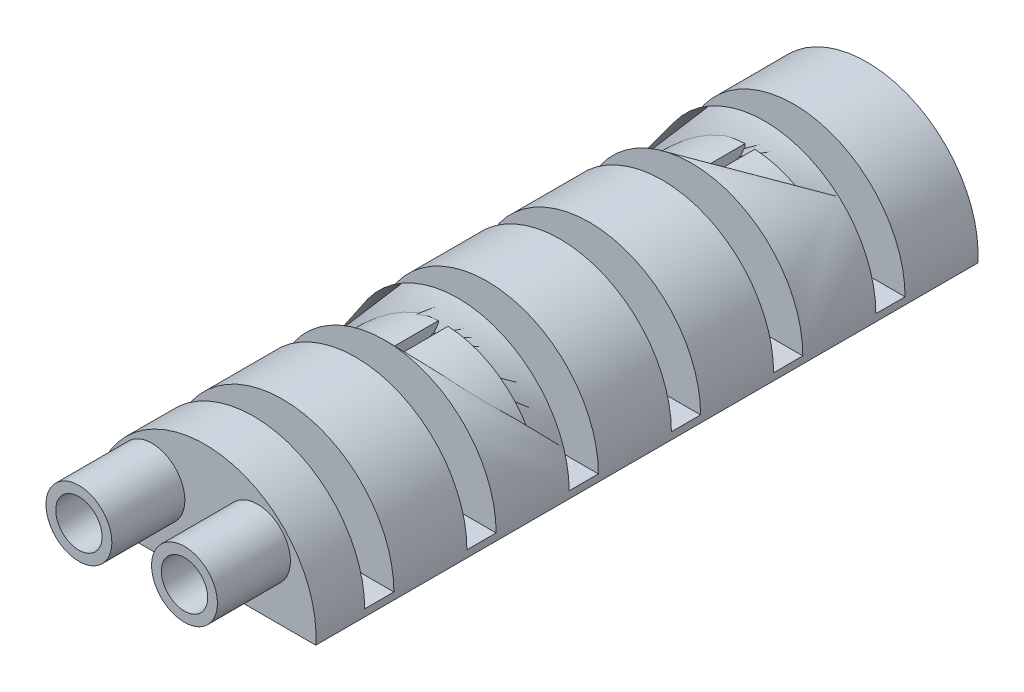
SolidWorks part; units mm, degrees
material "RUBBER 65A"
ref_plane "Front Plane" through (0, 0, 0) normal (0, 0, 1) x (1, 0, 0)
ref_plane "Top Plane" through (0, 0, 0) normal (0, 1, 0) x (1, 0, 0)
ref_plane "Right Plane" through (0, 0, 0) normal (1, 0, 0) x (0, 0, -1)
sketch "Sketch3" plane through (0, 0, 0) normal (0, 0, 1) x (1, 0, 0)
  circle A0 centre (0, 0) radius 22.86
  dimension "D1" = 45.72
extrude "Boss-Extrude2" add sketch "Sketch3" along normal blind 175
ref_axis "Axis2" through (0, 0, 174.1287) along (0, 0, -1)
sketch "Sketch5" plane through (0, 0, 175) normal (0, 0, 1) x (1, 0, 0)
  circle A0 centre (0, 0) radius 3.175
  dimension "D1" = 6.35
extrude "Cut-Extrude1" cut sketch "Sketch5" against normal through all contours A0
sketch "Sketch4" plane through (0, 0, 0) normal (0, 1, 0) x (1, 0, 0)
  line L0 (0, -175) -> (0, 0) construction
  line L1 (-22.86, -175) -> (22.86, -175) construction
  line L3 (-27.5, -165) -> (-11.5, -165)
  line L4 (-27.5, -165) -> (-27.5, -159)
  line L5 (-27.5, -159) -> (-11.5, -159)
  line L6 (-11.5, -165) -> (-11.5, -159)
  line L63 (-27.5, -144) -> (-27.5, -138)
  line L64 (-27.5, -144) -> (-11.5, -144)
  line L65 (-11.5, -144) -> (-11.5, -138)
  line L66 (-27.5, -138) -> (-11.5, -138)
  line L67 (-27.5, -123) -> (-27.5, -117)
  line L68 (-27.5, -123) -> (-11.5, -123)
  line L69 (-11.5, -123) -> (-11.5, -117)
  line L70 (-27.5, -117) -> (-11.5, -117)
  line L71 (-27.5, -102) -> (-27.5, -96)
  line L72 (-27.5, -102) -> (-11.5, -102)
  line L73 (-11.5, -102) -> (-11.5, -96)
  line L74 (-27.5, -96) -> (-11.5, -96)
  line L75 (-27.5, -81) -> (-27.5, -75)
  line L76 (-27.5, -81) -> (-11.5, -81)
  line L77 (-11.5, -81) -> (-11.5, -75)
  line L78 (-27.5, -75) -> (-11.5, -75)
  line L79 (-27.5, -60) -> (-27.5, -54)
  line L80 (-27.5, -60) -> (-11.5, -60)
  line L81 (-11.5, -60) -> (-11.5, -54)
  line L82 (-27.5, -54) -> (-11.5, -54)
  line L83 (-27.5, -39) -> (-27.5, -33)
  line L84 (-27.5, -39) -> (-11.5, -39)
  line L85 (-11.5, -39) -> (-11.5, -33)
  line L86 (-27.5, -33) -> (-11.5, -33)
  line L87 (-27.5, -18) -> (-27.5, -12)
  line L88 (-27.5, -18) -> (-11.5, -18)
  line L89 (-11.5, -18) -> (-11.5, -12)
  line L90 (-27.5, -12) -> (-11.5, -12)
  line L91 (-27.5, -165) -> (-27.5, -144) construction
  dimension "D1" = 10
  dimension "D2" = 6
  dimension "D3" = 27.5
  dimension "D4" = 16
  dimension "D6" = 21
  dimension "D5" = 8
revolve "Cut-Revolve1" cut sketch "Sketch4" angle 360 about L0
shell "Shell1" thickness 3
sketch "Sketch10" plane through (0, 0, 0) normal (0, 0, -1) x (-1, 0, 0)
  line L0 (0, 22.86) -> (0, -22.86) construction
  line L1 (-22.86, 0) -> (22.86, 0) construction
  line L2 (-1, 22.8381) -> (-1, 3.0134)
  line L3 (1, 3.0134) -> (1, 22.8381)
  line L4 (3.0134, 1) -> (22.8381, 1)
  line L5 (3.0134, -1) -> (22.8381, -1)
  line L6 (-1, -3.0134) -> (-1, -22.8381)
  line L7 (1, -3.0134) -> (1, -22.8381)
  line L8 (-22.8381, -1) -> (-3.0134, -1)
  line L9 (-22.8381, 1) -> (-3.0134, 1)
  circle A0 centre (0, 0) radius 22.86 construction
  circle A1 centre (0, 0) radius 3.175 construction
  arc A2 (-1, -22.8381) -> (1, -22.8381) centre (0, 0) ccw
  arc A3 (22.8381, -1) -> (22.8381, 1) centre (0, 0) ccw
  arc A4 (1, 22.8381) -> (-1, 22.8381) centre (0, 0) ccw
  arc A5 (-22.8381, 1) -> (-22.8381, -1) centre (0, 0) ccw
  arc A6 (-1, -3.0134) -> (1, -3.0134) centre (0, 0) ccw
  arc A7 (-3.0134, 1) -> (-3.0134, -1) centre (0, 0) ccw
  arc A8 (1, 3.0134) -> (-1, 3.0134) centre (0, 0) ccw
  arc A9 (3.0134, -1) -> (3.0134, 1) centre (0, 0) ccw
  dimension "D1" = 1
  dimension "D2" = 1
  dimension "D3" = 1
  dimension "D4" = 1
  dimension "D5" = 1
extrude "Boss-Extrude3" add sketch "Sketch10" against normal up to surface (175 mm away) up to face at (3.175, 0, 175)
sketch "Sketch11" plane through (0, 0, 0) normal (1, 0, 0) x (0, 0, -1)
  line L0 (-117, 22.8381) -> (-117, 1) construction
  line L1 (-165, 30.0791) -> (-159, 30.0791)
  line L2 (-165, 30.0791) -> (-165, 11.4564)
  line L3 (-165, 11.4564) -> (-159, 11.4564)
  line L4 (-159, 30.0791) -> (-159, 11.4564)
  line L5 (-144, 30.0191) -> (-138, 30.0191)
  line L6 (-144, 30.0191) -> (-144, 11.4564)
  line L7 (-144, 11.4564) -> (-138, 11.4564)
  line L8 (-138, 30.0191) -> (-138, 11.4564)
  line L9 (-123, 30.1992) -> (-117, 30.1992)
  line L10 (-123, 30.1992) -> (-123, 11.4755)
  line L11 (-123, 11.4755) -> (-117, 11.4755)
  line L12 (-117, 30.1992) -> (-117, 11.4755)
  line L13 (-117, 11.4564) -> (-117, 1) construction
  line L14 (-75, 11.4564) -> (-75, 1) construction
  line L15 (-102, 30.5593) -> (-96, 30.5593)
  line L16 (-102, 30.5593) -> (-102, 11.4564)
  line L17 (-102, 11.4564) -> (-96, 11.4564)
  line L18 (-96, 30.5593) -> (-96, 11.4564)
  line L19 (-81, 30.9195) -> (-75, 30.9195)
  line L20 (-81, 30.9195) -> (-81, 11.4755)
  line L21 (-81, 11.4755) -> (-75, 11.4755)
  line L22 (-75, 30.9195) -> (-75, 11.4755)
  line L23 (-75, 22.8381) -> (-75, 1) construction
  line L25 (-60, 31.9241) -> (-54, 31.9241)
  line L26 (-60, 31.9241) -> (-60, 11.4564)
  line L27 (-60, 11.4564) -> (-54, 11.4564)
  line L28 (-54, 31.9241) -> (-54, 11.4564)
  line L29 (-39, 30.6232) -> (-33, 30.6232)
  line L30 (-39, 30.6232) -> (-39, 11.4564)
  line L31 (-39, 11.4564) -> (-33, 11.4564)
  line L32 (-33, 30.6232) -> (-33, 11.4564)
  line L33 (-18, 31.5847) -> (-12, 31.5847)
  line L34 (-18, 31.5847) -> (-18, 11.4564)
  line L35 (-18, 11.4564) -> (-12, 11.4564)
  line L36 (-12, 31.5847) -> (-12, 11.4564)
revolve "Cut-Revolve2" cut sketch "Sketch11" angle 360 about axis through (0, 0, 174.1287) along (0, 0, -1)
sketch "Sketch12" plane through (0, 0, 0) normal (0, 1, 0) x (1, 0, 0)
  line L0 (19.8348, -172) -> (6.0935, -172) construction
  line L1 (24.7296, -168) -> (23.4796, -168)
  line L2 (24.7296, -168) -> (24.7296, -172)
  line L3 (24.7296, -172) -> (23.4796, -172)
  line L4 (23.4796, -168) -> (23.4796, -172)
  line L5 (0, 0) -> (0, -175) construction
  line L6 (-3.175, -175) -> (3.175, -175) construction
  line L7 (19.8348, -156) -> (8.441, -156) construction
  line L8 (19.8348, -9) -> (8.441, -9) construction
  line L9 (24.7296, -3) -> (23.4796, -3)
  line L10 (24.7296, -3) -> (24.7296, -9)
  line L11 (24.7296, -9) -> (23.4796, -9)
  line L12 (23.4796, -3) -> (23.4796, -9)
  line L13 (24.7296, -147) -> (23.4796, -147)
  line L14 (24.7296, -147) -> (24.7296, -156)
  line L15 (24.7296, -156) -> (23.4796, -156)
  line L16 (23.4796, -147) -> (23.4796, -156)
  line L17 (19.8348, -135) -> (8.441, -135) construction
  line L18 (24.7296, -126) -> (23.4796, -126)
  line L19 (24.7296, -126) -> (24.7296, -135)
  line L20 (24.7296, -135) -> (23.4796, -135)
  line L21 (23.4796, -126) -> (23.4796, -135)
  line L22 (19.8348, -114) -> (8.441, -114) construction
  line L23 (24.7296, -105) -> (23.4796, -105)
  line L24 (24.7296, -105) -> (24.7296, -114)
  line L25 (24.7296, -114) -> (23.4796, -114)
  line L26 (23.4796, -105) -> (23.4796, -114)
  line L27 (19.8348, -93) -> (8.441, -93) construction
  line L28 (24.7296, -84) -> (23.4796, -84)
  line L29 (24.7296, -84) -> (24.7296, -93)
  line L30 (24.7296, -93) -> (23.4796, -93)
  line L31 (23.4796, -84) -> (23.4796, -93)
  line L32 (19.8348, -72) -> (8.441, -72) construction
  line L33 (24.7296, -63) -> (23.4796, -63)
  line L34 (24.7296, -63) -> (24.7296, -72)
  line L35 (24.7296, -72) -> (23.4796, -72)
  line L36 (23.4796, -63) -> (23.4796, -72)
  line L37 (19.8348, -51) -> (8.441, -51) construction
  line L38 (24.7296, -42) -> (23.4796, -42)
  line L39 (24.7296, -42) -> (24.7296, -51)
  line L40 (24.7296, -51) -> (23.4796, -51)
  line L41 (23.4796, -42) -> (23.4796, -51)
  line L42 (19.8348, -30) -> (8.441, -30) construction
  line L43 (24.7296, -21) -> (23.4796, -21)
  line L44 (24.7296, -21) -> (24.7296, -30)
  line L45 (24.7296, -30) -> (23.4796, -30)
  line L46 (23.4796, -21) -> (23.4796, -30)
  dimension "D1" = 1.25
  dimension "D2" = 1.25
  dimension "D3" = 1.25
  dimension "D4" = 1.25
  dimension "D5" = 1.25
  dimension "D6" = 1.25
  dimension "D7" = 1.25
  dimension "D8" = 1.25
  dimension "D9" = 1.25
ref_plane "Plane1" through (0, 0, 0) normal (-0.7071, -0.7071, 0) x (0, 0, -1)
ref_plane "Plane2" through (0, 0, 0) normal (-0.7071, 0.7071, 0) x (0, 0, -1)
sketch "Sketch13" plane through (0, 0, 175) normal (0, 0, 1) x (1, 0, 0)
  line L0 (0, 22.86) -> (0, -22.86) construction
  line L1 (22.86, 0) -> (-22.86, 0) construction
  line L2 (0, 0) -> (16.1645, 16.1645) construction
  line L3 (22.3322, 22.3322) -> (-22.3322, -22.3322) construction
  circle A0 centre (10.8453, 10.8453) radius 6.7625
  circle A1 centre (10.8453, 10.8453) radius 4.7625
  circle A2 centre (0, 0) radius 15.3375 construction
  circle A3 centre (0, 0) radius 22.86 construction
  dimension "D1" = 2
  dimension "D2" = 9.525
  dimension "D3" = 30.675
extrude "Boss-Extrude4" add sketch "Sketch13" along normal blind 15
sketch "Sketch14" plane through (0, 0, 190) normal (0, 0, 1) x (1, 0, 0)
  circle A0 centre (10.8453, 10.8453) radius 4.7625
  dimension "D1" = 9.525
extrude "Cut-Extrude2" cut sketch "Sketch14" against normal blind 18
pattern_circular "CirPattern1" count 2 over 90 about axis through (0, 0, 174.1287) along (0, 0, -1) of "Boss-Extrude4", "Cut-Extrude2"
sketch "Sketch15" plane through (0, 0, 0) normal (0, 0, -1) x (-1, 0, 0)
  circle A0 centre (0, 0) radius 26.7427
extrude "Cut-Extrude3" cut sketch "Sketch15" against normal up to surface (39 mm away)
sketch "Sketch16" plane through (0, 0, 39) normal (0, 0, -1) x (-1, 0, 0)
  circle A0 centre (0, 0) radius 8.5
  circle A1 centre (0, 0) radius 3.175
extrude "Boss-Extrude6" add sketch "Sketch16" against normal up to surface (3 mm away) up to face at (-8.7979, 8.7979, 42)
sketch "Sketch17" plane through (0, 0, 175) normal (0, 0, 1) x (1, 0, 0)
  line L0 (-3.1748, 0) -> (-22.86, 0)
  line L1 (3.1748, 0) -> (22.86, 0)
  arc A0 (-22.86, 0) -> (22.86, 0) centre (0, 0) ccw
  arc A1 (-3.1748, 0) -> (3.1748, 0) centre (0, 0) ccw
  circle A2 centre (0, 0) radius 22.86 construction
  point P10 (0, 0)
  circle M1 centre (0, 0) radius 22.86
  circle M5 centre (0, 0) radius 3.175
  dimension "D1" = 3.1748
extrude "Boss-Extrude7" add sketch "Sketch17" against normal blind 136 contours L1 L0 M5 M1
sketch "Sketch21" plane through (0, 0, 175) normal (0, 0, 1) x (1, 0, 0)
  line L0 (-6.1748, 0) -> (-22.86, 0)
  line L1 (-3.1748, 0) -> (-22.86, 0) construction
  line L2 (6.1748, 0) -> (22.86, 0)
  line L3 (3.1748, 0) -> (22.86, 0) construction
  line L4 (-21.1674, 0) -> (-21.1674, -1.5)
  line L5 (-21.1674, -1.5) -> (-5.9898, -1.5)
  line L6 (-5.9898, -1.5) -> (-22.8107, -1.5)
  line L7 (18.0246, 0) -> (18.0246, -1.5)
  line L8 (18.0246, -1.5) -> (5.9898, -1.5)
  line L9 (5.9898, -1.5) -> (22.8107, -1.5)
  arc A0 (-6.1748, 0) -> (6.1748, 0) centre (0, 0) ccw
  arc A1 (-22.86, 0) -> (22.86, 0) centre (0, 0) ccw
  arc A2 (-22.86, 0) -> (22.86, 0) centre (0, 0) ccw construction
  circle M1 centre (0, 0) radius 22.86
  dimension "D1" = 6.1748
extrude "Cut-Extrude6" cut sketch "Sketch21" against normal blind 144.526 contours A0 L0 L2 M1
equation "\"inwall\"= .75"
equation "\"outwall\"=2"
